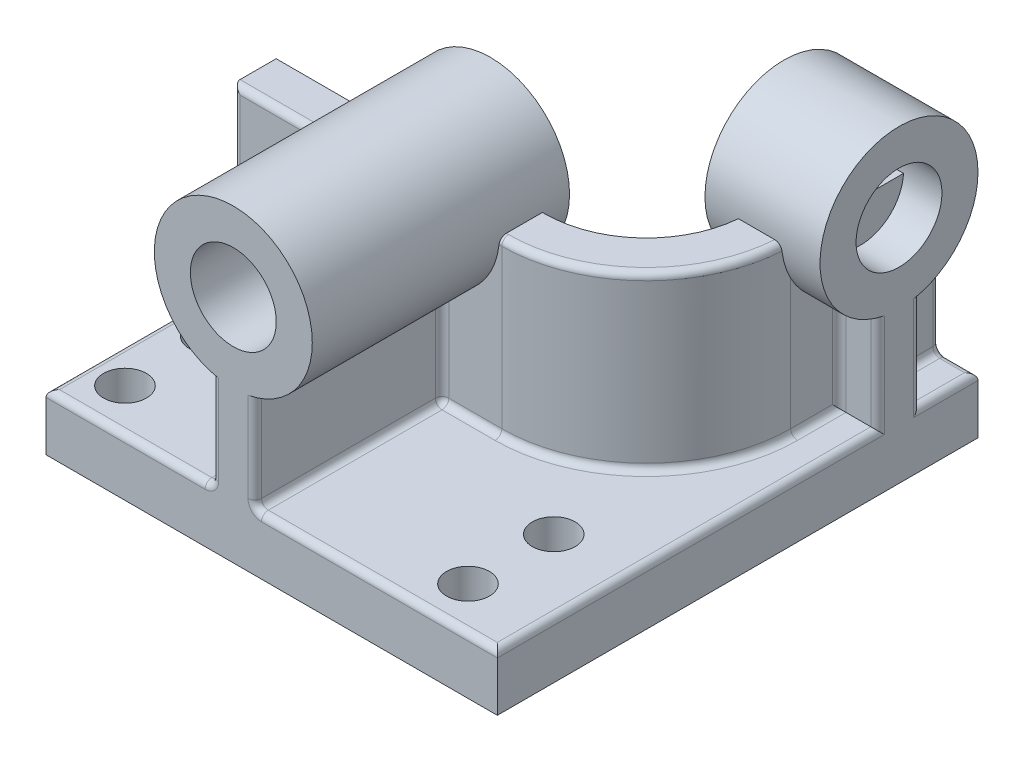
SolidWorks part; units mm, degrees
ref_plane "Front Plane" through (0, 0, 0) normal (0, 0, 1) x (1, 0, 0)
ref_plane "Top Plane" through (0, 0, 0) normal (0, 1, 0) x (1, 0, 0)
ref_plane "Right Plane" through (0, 0, 0) normal (1, 0, 0) x (0, 0, -1)
sketch "Sketch1" plane through (0, 0, 0) normal (0, 1, 0) x (1, 0, 0)
  line L0 (0, 0) -> (-84998.4055, 0) construction
  line L1 (0, 0) -> (0, -84998.4055) construction
  line L3 (-100, 106.5) -> (100, 106.5)
  line L4 (-100, 106.5) -> (-100, -106.5)
  line L5 (-100, -106.5) -> (100, -106.5)
  line L6 (100, 106.5) -> (100, -106.5)
  line L7 (0, -106.5) -> (0, 106.5) construction
  line L8 (-100, 0) -> (100, 0) construction
  circle A0 centre (68, -49.5) radius 9.5
  circle A1 centre (68, -87.5) radius 9.5
  circle A2 centre (-84, -49.5) radius 9.5
  circle A3 centre (-84, -87.5) radius 9.5
  point P5 (0, 0)
  point P20 (0, 0)
  point P21 (0, 0)
  point P22 (0, 0)
  point P23 (0, 0)
  dimension "D3" = 19
  dimension "D1" = 200
  dimension "D2" = 213
  dimension "D4" = 19
  dimension "D5" = 32
  dimension "D6" = 38
  dimension "D7" = 152
extrude "Boss-Extrude1" add sketch "Sketch1" along normal blind 25
sketch "Sketch2" plane through (0, 0, 106.5) normal (0, 0, 1) x (1, 0, 0)
  line L0 (-100, 0) -> (100, 0) construction
  line L1 (-100, 25) -> (-100, 0) construction
  circle A0 centre (-17, 102) radius 19.03
  circle A1 centre (-17, 102) radius 35
  dimension "D1" = 70
  dimension "D2" = 38.06
  dimension "D3" = 102
  dimension "D4" = 83
extrude "Boss-Extrude2" add sketch "Sketch2" against normal blind 114 separate body
sketch "Sketch3" plane through (100, 0, 0) normal (1, 0, 0) x (0, 0, -1)
  line L0 (106.5, 25) -> (106.5, 0) construction
  line L1 (-106.5, 0) -> (106.5, 0) construction
  line L2 (71.5, 67) -> (71.5, 25) construction
  line L3 (-106.5, 25) -> (106.5, 25) construction
  circle A0 centre (71.5, 102) radius 19.03
  circle A1 centre (71.5, 102) radius 35
  dimension "D1" = 70
  dimension "D2" = 38.06
  dimension "D3" = 35
  dimension "D4" = 102
extrude "Boss-Extrude3" add sketch "Sketch3" against normal blind 51 separate body
sketch "Sketch4" plane through (0, 25, 0) normal (0, 1, 0) x (1, 0, 0)
  line L1 (100, 106.5) -> (-100, 106.5) construction
  line L3 (-100, 106.5) -> (-100, -106.5) construction
  line L4 (-100, -23.5) -> (19, -23.5)
  line L5 (83, 40.5) -> (83, 106.5)
  line L6 (-119, -4.5) -> (19, -4.5) construction
  line L7 (-100, -4.5) -> (19, -4.5)
  line L8 (64, 40.5) -> (64, 106.5)
  line L9 (-100, -4.5) -> (-100, 106.5)
  line L10 (83, 106.5) -> (64, 106.5)
  line L11 (-100, -23.5) -> (-100, -4.5)
  line L12 (64, 40.5) -> (64, 125.5) construction
  line L13 (-119, -125.5) -> (-119, -4.5) construction
  line L14 (119, 125.5) -> (64, 125.5) construction
  line L15 (119, 106.5) -> (83, 106.5) construction
  line L16 (-100, -125.5) -> (-100, -23.5) construction
  line L17 (-100, 106.5) -> (64, 106.5)
  line L18 (-100, -106.5) -> (100, -106.5) construction
  line L19 (100, 36.5) -> (100, 106.5) construction
  arc A0 (83, 40.5) -> (19, -23.5) centre (19, 40.5) cw
  arc A1 (64, 40.5) -> (19, -4.5) centre (19, 40.5) cw
  line M6 (100, 106.5) -> (-100, 106.5)
  line M7 (-100, 106.5) -> (-100, -106.5)
  dimension "D3" = 64
  dimension "D1" = 102
  dimension "D2" = 36
  dimension "D4" = 19
extrude "Cut-Extrude1" cut sketch "Sketch4" against normal blind 51 contours A1 L8 L7 M6 M7 region at (-19.7596, 25, -52.1115)
extrude "Boss-Extrude4" add sketch "Sketch4<3>" along normal blind 76 contours L8 A1 L7 L4 A0 L5 M7 M6 region at (-97.7553, 25, 14)
sketch "Sketch4<3>" plane through (0, 25, 0) normal (0, 1, 0) x (1, 0, 0) same geometry as "Sketch4"
sketch "Sketch5" plane through (100, 0, 0) normal (1, 0, 0) x (0, 0, -1)
  line L0 (71.5, 67) -> (71.5, 20.0522) construction
  line L1 (81, 71.3695) -> (81, 25)
  line L2 (62, 71.3695) -> (62, 25)
  line L3 (62, 71.3695) -> (81, 71.3695)
  line L4 (81, 25) -> (62, 25)
  line L7 (-106.5, 25) -> (106.5, 25) construction
  circle A0 centre (71.5, 102) radius 35 construction
  arc A1 (40.5, 85.7519) -> (106.4857, 101) centre (71.5, 102) ccw construction
  dimension "D1" = 19
  dimension "D2" = 46.3695
extrude "Boss-Extrude5" add sketch "Sketch5" against normal up to surface (17 mm away) up to face at (83, 62.4549, -81.2746)
sketch "Sketch6" plane through (0, 0, 106.5) normal (0, 0, 1) x (1, 0, 0)
  line L0 (-17, 67) -> (-17, 7.6428) construction
  line L1 (-7.5, 71.4713) -> (-7.5, 25)
  line L2 (-26.5, 71.4713) -> (-26.5, 25)
  line L3 (-26.5, 71.4713) -> (-7.5, 71.4713)
  line L4 (-7.5, 25) -> (-26.5, 25)
  line L6 (-100, 25) -> (100, 25) construction
  arc A0 (-51.9857, 101) -> (17.9857, 101) centre (-17, 102) ccw construction
  circle A1 centre (-17, 102) radius 35 construction
  dimension "D1" = 19
  dimension "D2" = 46.4713
extrude "Boss-Extrude6" add sketch "Sketch6" along normal up to surface (-83 mm away) up to face at (-32.6667, 70, 23.5)
fillet "Fillet3" radius 3 26 edges at (83, 63, -106.5) (-7.5, 46.657, 106.5) (-26.5, 46.657, 106.5) (-100, 25, 65) (18.4929, 101, 23.5) (83, 25, -51.25) (5.75, 25, 23.5) (100, 25, -93.75) (91.5, 25, -106.5) (83, 25, -93.75) (83, 46.657, -81) (100, 46.657, -81) (100, 46.657, -62) (83, 46.657, -62) (62.823, 101, 6.1427) (64.2548, 25, 4.7548) (100, 25, 22.25) (46.25, 25, 106.5) (-7.5, 46.657, 23.5) (-7.5, 25, 65) (-63.25, 25, 106.5) (-63.25, 25, 23.5) (-26.5, 25, 65) (-26.5, 46.657, 23.5) (-100, 63, 23.5) (-75.9929, 101, 23.5)
